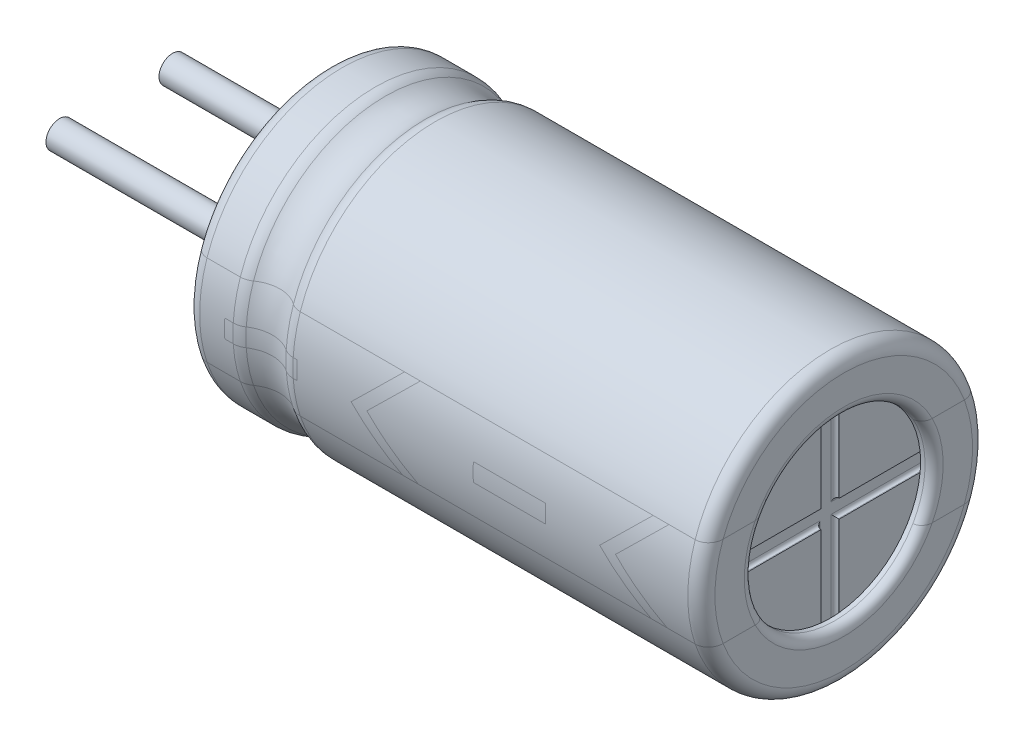
SolidWorks part; units mm, degrees
ref_plane "Front Plane" through (0, 0, 0) normal (0, 0, 1) x (1, 0, 0)
ref_plane "Top Plane" through (0, 0, 0) normal (0, 1, 0) x (1, 0, 0)
ref_plane "Right Plane" through (0, 0, 0) normal (1, 0, 0) x (0, 0, -1)
sketch "Эскиз1" plane through (0, 0, 0) normal (0, 1, 0) x (1, 0, 0)
  line L0 (-17.2337, 0) -> (16.838, 0) construction
  line L1 (0, 0) -> (0, 3.15)
  line L2 (0, 3.15) -> (1.1708, 3.15)
  line L3 (11.4, 3.15) -> (11.4, 0)
  line L4 (11.4, 0) -> (0, 0)
  line L5 (2.2292, 3.15) -> (11.4, 3.15)
  arc A0 (1.1708, 3.15) -> (2.2292, 3.15) centre (1.7, 3.75) ccw
  dimension "D3" = 1.6
  dimension "D1" = 3.15
  dimension "D2" = 11.4
  dimension "D4" = 1.7
  dimension "D5" = 0.6
revolve "Повернуть1" add sketch "Эскиз1" angle 360 about L0
fillet "Скругление1" radius 0.4 2 edges at (2.2292, 0, 3.15) (1.1708, 0, 3.15)
sketch "Эскиз2" plane through (11.4, 0, 0) normal (1, 0, 0) x (0, 0, -1)
  line L0 (0, 3.4063) -> (0, -3.6242) construction
  line L1 (-3.4972, 0) -> (3.5584, 0) construction
  circle A0 centre (0, 0) radius 2
  dimension "D1" = 4
extrude "Вырез-Вытянуть1" cut sketch "Эскиз2" against normal blind 0.3
fillet "Скругление2" radius 0.2 1 edges at (11.4, 0, -2)
fillet "Скругление3" radius 0.3 1 edges at (11.4, 0, 3.15)
sketch "Эскиз3" plane through (11.1, 0, 0) normal (1, 0, 0) x (0, 0, -1)
  line L0 (0, 3.4147) -> (0, -3.4901) construction
  line L1 (-3.5223, 0) -> (3.4327, 0) construction
  line L2 (-0.2, 2.3648) -> (-0.2, 0.2)
  line L3 (-0.2, 0.2) -> (-2.3648, 0.2)
  line L4 (0.2, 0.2) -> (2.3648, 0.2)
  line L5 (0.2, 2.3648) -> (0.2, 0.2)
  line L6 (0.2, -0.2) -> (2.3648, -0.2)
  line L7 (0.2, -2.3648) -> (0.2, -0.2)
  line L8 (-0.2, -2.3648) -> (-0.2, -0.2)
  line L9 (-0.2, -0.2) -> (-2.3648, -0.2)
  circle A0 centre (0, 0) radius 2.3732 construction
  arc A1 (-2.3648, 0.2) -> (-2.3648, -0.2) centre (0, 0) ccw
  arc A2 (0.2, 2.3648) -> (-0.2, 2.3648) centre (0, 0) ccw
  arc A3 (2.3648, -0.2) -> (2.3648, 0.2) centre (0, 0) ccw
  arc A4 (-0.2, -2.3648) -> (0.2, -2.3648) centre (0, 0) ccw
  dimension "D1" = 0.2
  dimension "D2" = 0.2
extrude "Вырез-Вытянуть2" cut sketch "Эскиз3" against normal blind 0.1
sketch "Эскиз5" plane through (0, 0, 0) normal (-1, 0, 0) x (0, 0, 1)
  circle A0 centre (0, 0) radius 2
  dimension "D1" = 4
extrude "Вырез-Вытянуть3" cut sketch "Эскиз5" against normal blind 0.3
fillet "Скругление6" radius 0.3 2 edges at (0, 0, 2) (0, 0, 3.15)
sketch "Эскиз6" plane through (0.3, 0, 0) normal (-1, 0, 0) x (0, 0, 1)
  line L0 (-3.5152, 0) -> (3.4398, 0) construction
  line L1 (0, 3.3812) -> (0, -3.3644) construction
  circle A0 centre (-1.25, 0) radius 0.3
  circle A1 centre (1.25, 0) radius 0.3
  dimension "D1" = 0.6
  dimension "D2" = 1.25
extrude "Бобышка-Вытянуть1" add sketch "Эскиз6" along normal blind 5
fillet "Скругление7" radius 0.08 8 edges at (11, 1.2824, -0.2) (11, -1.2824, -0.2) (11, -0.2, -1.2824) (11, -0.2, 1.2824) (11, -1.2824, 0.2) (11, 1.2824, 0.2) (11, 0.2, -1.2824) (11, 0.2, 1.2824)
ref_plane "Плоскость1" through (0, 0, 3.5) normal (0, 0, 1) x (1, 0, 0)
sketch "Эскиз7" plane through (0, 0, 3.5) normal (0, 0, 1) x (1, 0, 0)
  line L0 (-2.8406, 0) -> (14.5012, 0) construction
  line L1 (0, 2.85) -> (0, -2.85) construction
  line L2 (-2, 1) -> (13, 1)
  line L3 (-2, 1) -> (-2, -1)
  line L4 (-2, -1) -> (13, -1)
  line L5 (13, 1) -> (13, -1)
  line L6 (10.5206, 1) -> (9.5, 0)
  line L7 (9.5, 0) -> (10.4798, -1)
  line L8 (10.4798, -1) -> (10.1298, -1)
  line L9 (10.1298, -1) -> (9.15, 0)
  line L10 (9.15, 0) -> (10.1706, 1)
  line L11 (10.1706, 1) -> (10.5206, 1)
  line L12 (4.6706, 1) -> (5.0206, 1)
  line L13 (6.35, 0.2) -> (7.95, 0.2)
  line L14 (6.35, 0.2) -> (6.35, -0.2)
  line L15 (6.35, -0.2) -> (7.95, -0.2)
  line L16 (7.95, 0.2) -> (7.95, -0.2)
  line L17 (6.35, 0.2) -> (7.95, -0.2) construction
  line L18 (6.35, -0.2) -> (7.95, 0.2) construction
  line L21 (4.9798, -1) -> (4.6298, -1)
  line L28 (-0.8294, 1) -> (-0.4794, 1)
  line L31 (-0.5202, -1) -> (-0.8702, -1)
  line L34 (-4.65, 0.2) -> (-4.65, -0.2)
  line L35 (-4.65, 0.2) -> (-3.05, 0.2)
  line L36 (-3.05, 0.2) -> (-3.05, -0.2)
  line L37 (-4.65, -0.2) -> (-3.05, -0.2)
  line L38 (-0.8702, -1) -> (-1.85, 0) [skipped]
  line L39 (-1.5, 0) -> (-0.5202, -1) [skipped]
  line L40 (-0.4794, 1) -> (-1.5, 0) [skipped]
  line L41 (-1.85, 0) -> (-0.8294, 1) [skipped]
  line L42 (0.85, 0.2) -> (0.85, -0.2) [skipped]
  line L43 (0.85, -0.2) -> (2.45, -0.2) [skipped]
  line L44 (2.45, 0.2) -> (2.45, -0.2) [skipped]
  line L45 (0.85, 0.2) -> (2.45, 0.2) [skipped]
  line L46 (4.6298, -1) -> (3.65, 0) [skipped]
  line L47 (4, 0) -> (4.9798, -1) [skipped]
  line L48 (5.0206, 1) -> (4, 0) [skipped]
  line L49 (3.65, 0) -> (4.6706, 1) [skipped]
  line L50 (0.85, 0.2) -> (0.85, -0.2)
  line L51 (0.85, 0.2) -> (2.45, 0.2)
  line L52 (2.45, 0.2) -> (2.45, -0.2)
  line L53 (0.85, -0.2) -> (2.45, -0.2)
  line L54 (4.6706, 1) -> (5.0206, 1)
  line L55 (5.0206, 1) -> (4, 0)
  line L56 (4, 0) -> (4.9798, -1)
  line L57 (4.9798, -1) -> (4.6298, -1)
  line L58 (4.6298, -1) -> (3.65, 0)
  line L59 (3.65, 0) -> (4.6706, 1)
  point P9 (13, 0)
  point P12 (7.15, 0)
  dimension "D1" = 15
  dimension "D2" = 2
  dimension "D3" = 2
  dimension "D4" = 0.25
  dimension "D5" = 3.5
  dimension "D6" = 1.4
  dimension "D7" = 1.6
  dimension "D8" = 0.4
  dimension "D9" = 1.2
  dimension "D10" = 3
  dimension "D11" = 2
split line "Разделяющая линия1"
